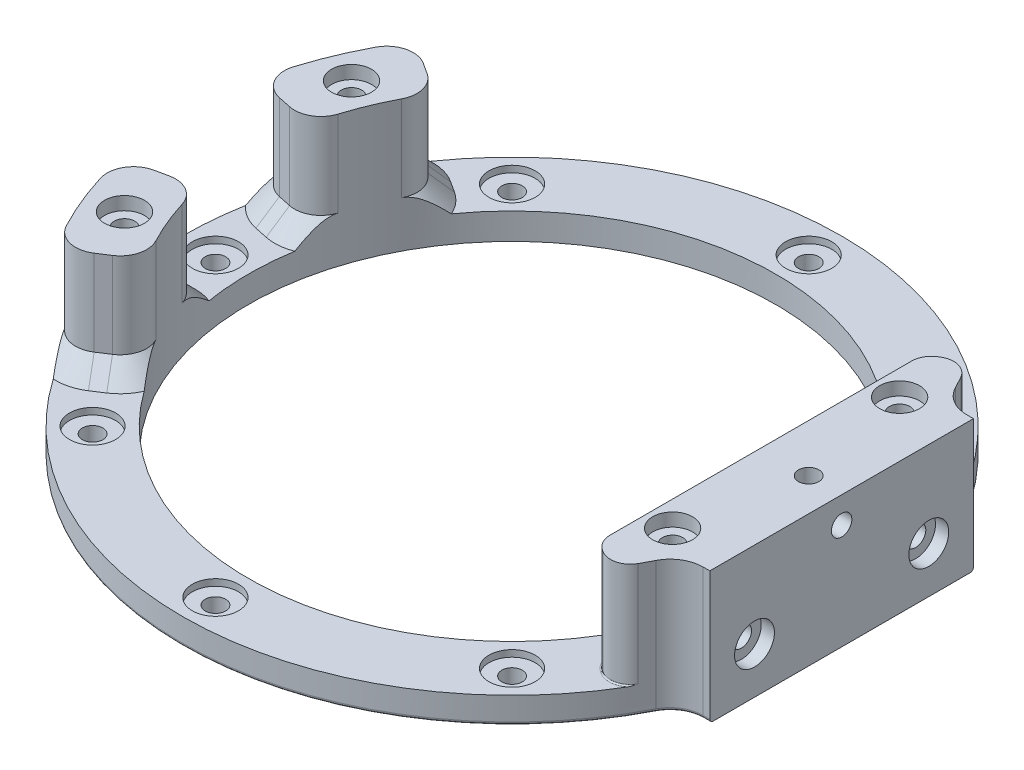
SolidWorks part; units mm, degrees
material "6061 合金"
ref_plane "前视基准面" through (0, 0, 0) normal (0, 0, 1) x (1, 0, 0)
ref_plane "上视基准面" through (0, 0, 0) normal (0, 1, 0) x (1, 0, 0)
ref_plane "右视基准面" through (0, 0, 0) normal (1, 0, 0) x (0, 0, -1)
sketch "草图1" plane through (0, 0, 0) normal (0, 1, 0) x (1, 0, 0)
  circle A0 centre (0, 0) radius 50
  dimension "D1" = 100
extrude "凸台-拉伸1" add sketch "草图1" along normal mid plane 40
sketch "草图2" plane through (0, 20, 0) normal (0, 1, 0) x (1, 0, 0)
  circle A0 centre (0, 0) radius 29
  dimension "D1" = 58
extrude "切除-拉伸1" cut sketch "草图2" against normal up to next
sketch "草图3" plane through (0, 20, 0) normal (0, 1, 0) x (1, 0, 0)
  circle A0 centre (0, 45) radius 1.55
  dimension "D2" = 3.1
  dimension "D1" = 45
extrude "切除-拉伸2" cut sketch "草图3" against normal up to next
pattern_circular "阵列(圆周)1" count 8 over 360 about axis through (0, 20, 0) along (0, 1, 0) of "切除-拉伸2"
sketch "草图4" plane through (0, 20, 0) normal (0, 1, 0) x (1, 0, 0)
  circle A0 centre (0, 36.5) radius 1.5
  dimension "D2" = 3
  dimension "D1" = 36.5
extrude "切除-拉伸3" cut sketch "草图4" against normal up to next
pattern_circular "阵列(圆周)2" count 8 over 360 about axis through (0, 20, 0) along (0, 1, 0) of "切除-拉伸3"
sketch "草图5" plane through (0, -20, 0) normal (0, -1, 0) x (1, 0, 0)
  circle A0 centre (0, 0) radius 40
  dimension "D1" = 80
extrude "切除-拉伸4" cut sketch "草图5" against normal offset from surface (36 mm away) 4 up to face at (-35, 20, 0)
sketch "草图6" plane through (0, 0, 0) normal (0, 1, 0) x (1, 0, 0)
  line L0 (0, 0) -> (-80.7225, 0) construction
  line L1 (-39.1259, -8.3165) -> (-48.9074, -10.3956)
  line L2 (-39.1259, 8.3165) -> (-48.9074, 10.3956)
  circle A0 centre (0, 0) radius 50 construction
  circle A1 centre (0, 0) radius 40 construction
  arc A2 (-48.9074, 10.3956) -> (-48.9074, -10.3956) centre (0, 0) ccw
  arc A3 (-39.1259, 8.3165) -> (-39.1259, -8.3165) centre (0, 0) ccw
  dimension "D1" = 24
  dimension "D2" = 12
extrude "切除-拉伸6" cut sketch "草图6" against normal mid plane 32
pattern_circular "阵列(圆周)3" count 8 over 360 about axis through (0, -20.001, 0) along (0, 1, 0) skipping 2, 4 of "切除-拉伸6"
ref_plane "基准面1" through (50, 0, 0) normal (1, 0, 0) x (0, 0, -1)
sketch "草图10" plane through (50, 0, 0) normal (1, 0, 0) x (0, 0, -1)
  line L0 (-50, -20) -> (50, -20) construction
  line L1 (-20, 20) -> (20, 20)
  line L2 (-20, 20) -> (-20, -20)
  line L3 (-20, -20) -> (20, -20)
  line L4 (20, 20) -> (20, -20)
  line L5 (-20, 20) -> (20, -20) construction
  line L6 (-20, -20) -> (20, 20) construction
  point P0 (0, 0)
  dimension "D1" = 40
extrude "凸台-拉伸5" add sketch "草图10" against normal up to surface (4.1742 mm away) up to face at (34.969, 0, -34.969)
ref_plane "基准面2" through (70, 0, 0) normal (1, 0, 0) x (0, 0, -1)
sketch "草图14" plane through (0, 0, 0) normal (0, 1, 0) x (1, 0, 0)
  line L0 (45, 0) -> (-45, 0) construction
  line L1 (-27.232, -41.9335) -> (-21.7856, -33.5468) construction
  line L2 (-27.232, 41.9335) -> (-21.7856, 33.5468)
  line L3 (41.9335, 27.232) -> (33.5468, 21.7856)
  line L5 (-27.232, -41.9335) -> (-21.7856, -33.5468)
  line L6 (41.9335, -27.232) -> (33.5468, -21.7856)
  line L8 (41.9335, -27.232) -> (33.5468, -21.7856) construction
  arc A0 (-21.7856, 33.5468) -> (33.5468, 21.7856) centre (0, 0) cw
  arc A1 (45.8258, 20) -> (45.8258, -20) centre (0, 0) ccw construction
  arc A2 (-27.232, 41.9335) -> (41.9335, 27.232) centre (0, 0) cw
  circle A3 centre (0, 0) radius 40 construction
  arc A4 (-27.232, -41.9335) -> (41.9335, -27.232) centre (0, 0) ccw
  arc A5 (-21.7856, -33.5468) -> (33.5468, -21.7856) centre (0, 0) ccw
extrude "切除-拉伸8" cut sketch "草图14" against normal up to surface (16 mm away) and the other way up to surface (16 mm away) up to face at (-31.4721, -16, -31.4721) other way up to face at (0, 16, -35)
sketch "草图15" plane through (0, -20, 0) normal (0, -1, 0) x (1, 0, 0)
  line L0 (0, 0) -> (-45, 0) construction
  line L1 (0, 0) -> (-31.8198, 31.8198) construction
  line L2 (0, 0) -> (-46.194, 19.1342) construction
  line L3 (0, 0) -> (0, -29) construction
  arc A0 (45.8258, 20) -> (45.8258, -20) centre (0, 0) ccw construction
  circle A1 centre (0, 0) radius 45 construction
  circle A2 centre (-41.5746, 17.2208) radius 1.55
  circle A3 centre (-41.5746, -17.2208) radius 1.55
  circle A4 centre (0, 0) radius 29 construction
  circle A5 centre (41.5746, -17.2208) radius 1.55
  circle A6 centre (41.5746, 17.2208) radius 1.55
  dimension "D2" = 3.1
  dimension "D1" = 22.5
extrude "切除-拉伸10" cut sketch "草图15" against normal through all
ref_plane "基准面3" through (43.5, 0, 0) normal (1, 0, 0) x (0, 0, -1)
sketch "草图36" plane through (0, -20, 0) normal (0, -1, 0) x (1, 0, 0)
  circle A0 centre (-41.5746, 17.2208) radius 3.5
  circle A1 centre (-41.5746, -17.2208) radius 3.5
  circle A2 centre (41.5746, 17.2208) radius 3.5
  circle A3 centre (41.5746, -17.2208) radius 3.5
  dimension "D1" = 7
  dimension "D2" = 7
  dimension "D3" = 7
  dimension "D4" = 7
extrude "切除-拉伸23" cut sketch "草图36" against normal blind 5
fillet "圆角4" radius 4 8 edges at (-41.9335, 0, -27.232) (-33.5468, 0, -21.7856) (-39.1259, 0, -8.3165) (-48.9074, 0, -10.3956) (-39.1259, 0, 8.3165) (-48.9074, 0, 10.3956) (-33.5468, 0, 21.7856) (-41.9335, 0, 27.232)
sketch "草图39" plane through (0, 20, 0) normal (0, 1, 0) x (1, 0, 0)
  line L1 (-69.5496, 69.5627) -> (120.7918, 69.5627)
  line L2 (-69.5496, 69.5627) -> (-69.5496, -71.1581)
  line L3 (-69.5496, -71.1581) -> (120.7918, -71.1581)
  line L4 (120.7918, 69.5627) -> (120.7918, -71.1581)
extrude "切除-拉伸26" cut sketch "草图39" against normal blind 20
sketch "草图40" plane through (0, 0, 0) normal (0, 1, 0) x (1, 0, 0)
  circle A0 centre (-41.5746, 17.2208) radius 3.025
  circle A1 centre (-41.5746, -17.2208) radius 3.025
  circle A2 centre (41.5746, -17.2208) radius 3.025
  circle A3 centre (41.5746, 17.2208) radius 3.025
  dimension "D1" = 6.05
  dimension "D2" = 6.05
  dimension "D3" = 6.05
  dimension "D4" = 6.05
extrude "切除-拉伸27" cut sketch "草图40" against normal blind 2
sketch "草图42" plane through (0, -16, 0) normal (0, 1, 0) x (1, 0, 0)
  circle A0 centre (-45, 0) radius 3.5
  circle A1 centre (-31.8198, 31.8198) radius 3.5
  circle A2 centre (0, 45) radius 3.5
  circle A3 centre (31.8198, 31.8198) radius 3.5
  circle A5 centre (31.8198, -31.8198) radius 3.5
  circle A6 centre (0, -45) radius 3.5
  circle A7 centre (-31.8198, -31.8198) radius 3.5
  circle A8 centre (45, 0) radius 3.5 [skipped]
  point P19 (0, 0)
  dimension "D1" = 7
  dimension "D2" = 8
extrude "切除-拉伸29" cut sketch "草图42" against normal blind 1
sketch "草图43" plane through (0, 0, 0) normal (0, 1, 0) x (1, 0, 0)
  line L0 (70.2101, 13.22) -> (7.8081, 13.22) construction
  line L1 (70.2101, -13.22) -> (14.8369, -13.22) construction
  line L2 (45.8258, 20) -> (50, 20) construction
  line L3 (50, -20) -> (45.8258, -20) construction
  line L4 (37.74, -13.22) -> (37.74, 30.2984) construction
  line L5 (37.6683, 13.22) -> (50, 13.22) construction
  line L6 (37.74, 27.093) -> (26.481, 27.093)
  line L7 (37.74, 27.093) -> (37.74, -25.8812)
  line L8 (37.74, -25.8812) -> (26.481, -25.8812)
  line L9 (26.481, 27.093) -> (26.481, -25.8812)
  line L10 (50, 20) -> (50, -20) construction
  point P14 (37.6683, 13.22)
  dimension "D1" = 6.78
  dimension "D2" = 6.78
  dimension "D3" = 12.26
extrude "切除-拉伸30" cut sketch "草图43" against normal up to surface (16 mm away) up to face at (31.8198, -16, 35.3198)
sketch "草图44" plane through (0, 0, 0) normal (0, 1, 0) x (1, 0, 0)
  line L0 (37.74, 13.2549) -> (37.74, -13.2549)
  arc A0 (37.74, -13.2549) -> (37.74, 13.2549) centre (0, 0) ccw construction
  arc A1 (37.74, -13.2549) -> (37.74, 13.2549) centre (0, 0) ccw
extrude "凸台-拉伸6" add sketch "草图44" against normal up to surface (20 mm away) up to face at (-41.5746, -20, -20.7208)
sketch "草图45" plane through (50, 0, 0) normal (1, 0, 0) x (0, 0, -1)
  line L0 (-13.22, 6.179) -> (-13.22, -28.2418) construction
  line L1 (13.22, 6.179) -> (13.22, -24.9728) construction
  line L2 (-20, 0) -> (-20, -20) construction
  line L3 (20, -20) -> (20, 0) construction
  line L4 (-20, -20) -> (20, -20) construction
  line L5 (20, 0) -> (-20, 0) construction
  circle A0 centre (-13.22, -13) radius 1.55
  circle A1 centre (13.22, -13) radius 1.55
  circle A2 centre (0, -4) radius 1.55
  dimension "D3" = 3.1
  dimension "D4" = 3.1
  dimension "D5" = 7
  dimension "D6" = 7
  dimension "D8" = 3.1
  dimension "D1" = 6.78
  dimension "D2" = 6.78
  dimension "D7" = 4
extrude "切除-拉伸31" cut sketch "草图45" against normal up to surface (12.26 mm away) up to face at (37.74, -13, 0)
sketch "草图46" plane through (50, 0, 0) normal (1, 0, 0) x (0, 0, -1)
  circle A0 centre (-13.22, -13) radius 3.025
  circle A1 centre (13.22, -13) radius 3.025
  dimension "D1" = 6.05
  dimension "D2" = 6.05
extrude "切除-拉伸32" cut sketch "草图46" against normal blind 2
fillet "圆角5" radius 10 2 edges at (37.74, -18, 13.2549) (37.74, -18, -13.2549)
fillet "圆角6" radius 5 2 edges at (45.8258, -10, 20) (45.8258, -10, -20)
fillet "圆角7" radius 3 4 edges at (41.9335, -8, -27.232) (37.74, -8, -24.5086) (37.74, -8, 24.5086) (41.9335, -8, 27.232)
chamfer "倒角1" distance 3 angle 45 12 edges at (-41.6124, -16, -25.4765) (-47.439, -16, 11.4098) (-41.6124, -16, 25.4765) (-40.005, -16, -9.5725) (-35.0566, -16, 21.519) (-37.5907, -16, 24.4117) (-40.005, -16, 9.5725) (-43.8423, -16, 9.319) (-43.8423, -16, -9.319) (-47.439, -16, -11.4098) (-35.0566, -16, -21.519) (-37.5907, -16, -24.4117)
fillet "圆角8" radius 0.2 8 edges at (41.6882, -16, -25.9429) (39.2216, -16, -25.4708) (38.1035, -16, -24.3113) (41.6882, -16, 25.9429) (39.2216, -16, 25.4708) (38.1035, -16, 24.3113) (37.74, -16, -17.1516) (37.74, -16, 17.1516)
fillet "圆角9" radius 0.5 5 edges at (49.4949, -20, -20) (49.4949, -20, 20) (46.3786, -20, 20.736) (46.3786, -20, -20.736) (-50, -20, 0)
